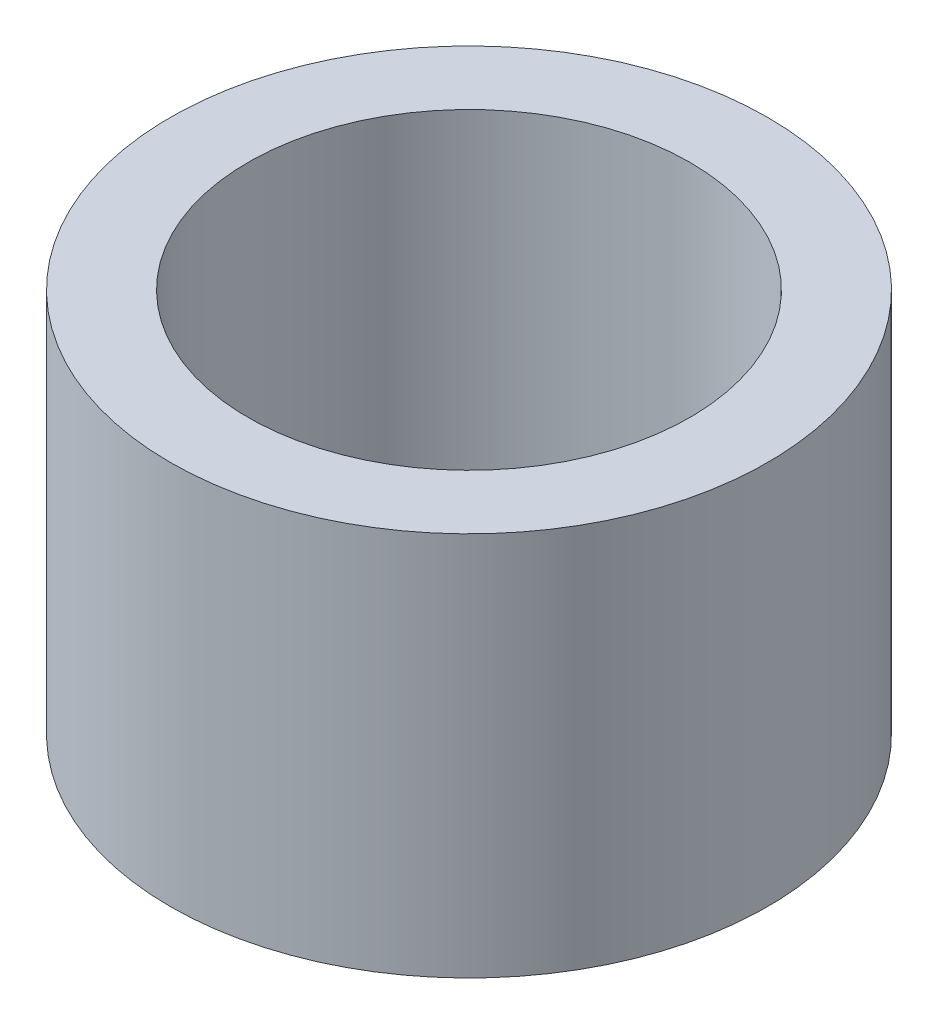
SolidWorks part; units mm, degrees
ref_plane "Front Plane" through (0, 0, 0) normal (0, 0, 1) x (1, 0, 0)
ref_plane "Top Plane" through (0, 0, 0) normal (0, 1, 0) x (1, 0, 0)
ref_plane "Right Plane" through (0, 0, 0) normal (1, 0, 0) x (0, 0, -1)
sketch "Sketch1" plane through (0, 0, 0) normal (0, 1, 0) x (1, 0, 0)
  circle A0 centre (0, 0) radius 22.5
  dimension "SLEEVE_OD" = 45
extrude "Boss-Extrude1" add sketch "Sketch1" along normal blind 28.9702
sketch "Sketch2" plane through (0, 0, 0) normal (0, 1, 0) x (1, 0, 0)
  circle A0 centre (0, 0) radius 16.6406
  dimension "BORE_D" = 33.2811
extrude "Cut-Extrude1" cut sketch "Sketch2" along normal through all
chamfer "Chamfer1" distance 2.5366 angle 64.437 rebuild error yes
